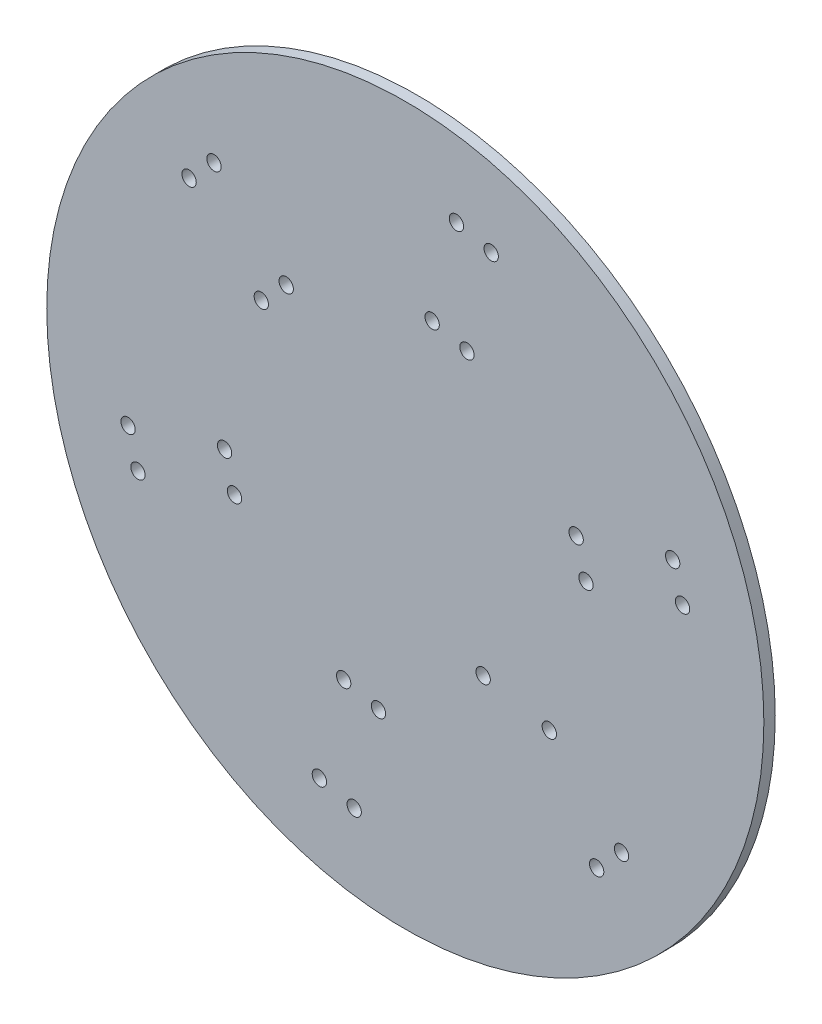
SolidWorks part; units mm, degrees
ref_plane "Front Plane" through (0, 0, 0) normal (0, 0, 1) x (1, 0, 0)
ref_plane "Top Plane" through (0, 0, 0) normal (0, 1, 0) x (1, 0, 0)
ref_plane "Right Plane" through (0, 0, 0) normal (1, 0, 0) x (0, 0, -1)
sketch "Sketch1" plane through (0, 0, 0) normal (0, 0, 1) x (1, 0, 0)
  circle A0 centre (0, 0) radius 100
  dimension "D1" = 200
extrude "Boss-Extrude1" add sketch "Sketch1" along normal blind 3.175
sketch "Sketch2" plane through (0, 0, 3.175) normal (0, 0, 1) x (1, 0, 0)
  line L0 (-71.9351, 69.4647) -> (71.9351, -69.4647) construction
  line L1 (-96.1257, -27.5653) -> (96.1257, 27.5653) construction
  line L2 (-24.1906, -97.03) -> (24.1906, 97.03) construction
  circle A0 centre (0, 0) radius 100 construction
  point P8 (0, 0)
  point P9 (0, 0)
  point P13 (0, 0)
  dimension "D1" = 60
  dimension "D2" = 60
sketch "Sketch6" plane through (0, 0, 3.175) normal (0, 0, 1) x (1, 0, 0)
  circle A0 centre (-14.2591, -77.8632) radius 2
  circle A1 centre (-23.9621, -75.4441) radius 2
  circle A2 centre (-7.4857, -50.6948) radius 2
  circle A3 centre (-17.1887, -48.2758) radius 2
  circle A4 centre (60.302, -51.2803) radius 2
  circle A5 centre (53.3555, -58.4738) radius 2
  circle A6 centre (21.7061, -27.8768) radius 2
  circle A7 centre (40.1601, -31.8302) radius 2
  circle A8 centre (77.3176, 16.9703) radius 2
  circle A9 centre (74.5611, 26.5829) radius 2
  circle A10 centre (47.6458, 18.8646) radius 2
  circle A11 centre (50.4024, 9.252) radius 2
  circle A12 centre (23.9621, 75.4441) radius 2
  circle A13 centre (14.2591, 77.8632) radius 2
  circle A14 centre (7.4857, 50.6948) radius 2
  circle A15 centre (17.1887, 48.2758) radius 2
  circle A16 centre (-33.2137, 39.0237) radius 2
  circle A17 centre (-40.1601, 31.8302) radius 2
  circle A18 centre (-60.302, 51.2803) radius 2
  circle A19 centre (-53.3555, 58.4738) radius 2
  circle A20 centre (-47.6458, -18.8646) radius 2
  circle A21 centre (-50.4024, -9.252) radius 2
  circle A22 centre (-74.5611, -26.5829) radius 2
  circle A23 centre (-77.3176, -16.9703) radius 2
  dimension "D1" = 4
extrude "Cut-Extrude1" cut sketch "Sketch6" against normal through all contours A8 | A9 | A11 | A10 | A15 | A14 | A12 | A13 | A16 | A17 | A19 | A18 | A21 | A20 | A23 | A22 | A2 | A3 | A0 | A1 | A7 | A4 | A5 | A6 region at (-14.2591, -77.8632, 3.175) region at (-23.9621, -75.4441, 3.175) region at (-7.4857, -50.6948, 3.175) region at (-17.1887, -48.2758, 3.175) region at (60.302, -51.2803, 3.175) region at (53.3555, -58.4738, 3.175) region at (21.7061, -27.8768, 3.175) region at (40.1601, -31.8302, 3.175) region at (77.3176, 16.9703, 3.175) region at (74.5611, 26.5829, 3.175) region at (47.6458, 18.8646, 3.175) region at (50.4024, 9.252, 3.175) region at (23.9621, 75.4441, 3.175) region at (14.2591, 77.8632, 3.175) region at (7.4857, 50.6948, 3.175) region at (17.1887, 48.2758, 3.175) region at (-33.2137, 39.0237, 3.175) region at (-40.1601, 31.8302, 3.175) region at (-60.302, 51.2803, 3.175) region at (-53.3555, 58.4738, 3.175) region at (-47.6458, -18.8646, 3.175) region at (-50.4024, -9.252, 3.175) region at (-74.5611, -26.5829, 3.175) region at (-77.3176, -16.9703, 3.175)
